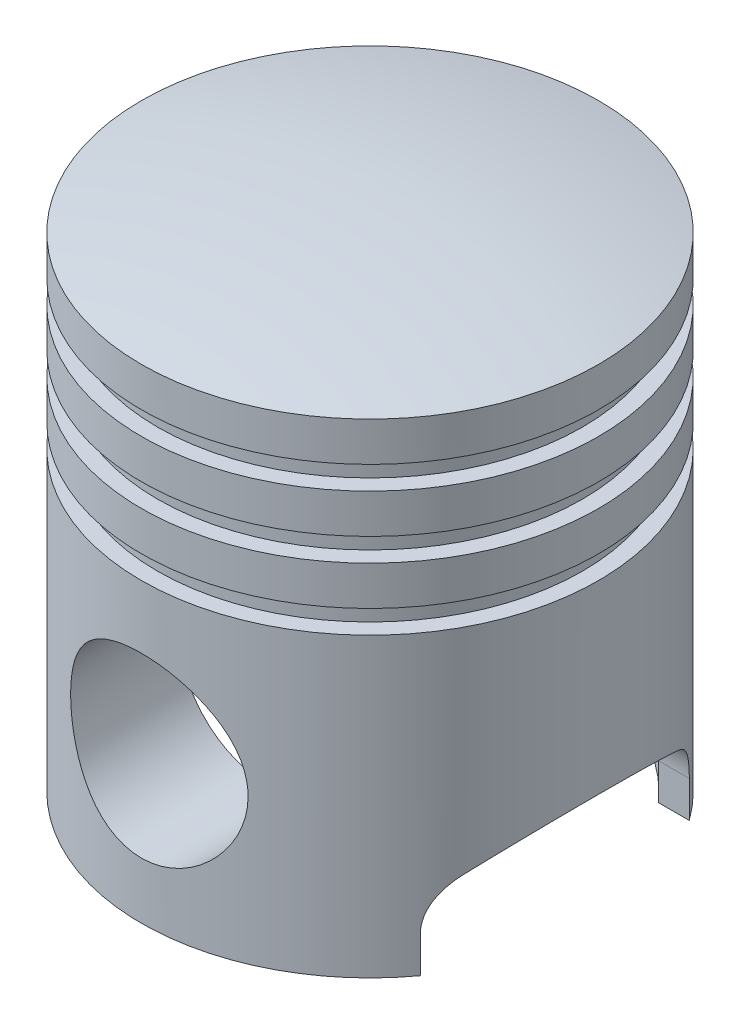
SolidWorks part; units mm, degrees
ref_plane "Front Plane" through (0, 0, 0) normal (0, 0, 1) x (1, 0, 0)
ref_plane "Top Plane" through (0, 0, 0) normal (0, 1, 0) x (1, 0, 0)
ref_plane "Right Plane" through (0, 0, 0) normal (1, 0, 0) x (0, 0, -1)
sketch "Sketch1" plane through (0, 0, 0) normal (0, 1, 0) x (1, 0, 0)
  circle A0 centre (0, 0) radius 42.5
  dimension "D1" = 85
extrude "Boss-Extrude3" add sketch "Sketch1" along normal blind 90
sketch "Sketch3" plane through (0, 90, 0) normal (0, 1, 0) x (1, 0, 0)
  circle A0 centre (0, 0) radius 39.5
  dimension "D1" = 79
extrude "Cut-Extrude2" cut sketch "Sketch3" against normal blind 4.3 from offset 7.3 flip side to cut offset against normal yes
pattern_linear "LPattern1" count 3 spacing 11.6 along (0, -1, 0) of "Cut-Extrude2"
sketch "Sketch4" plane through (0, 0, 0) normal (0, -1, 0) x (1, 0, 0)
  circle A0 centre (0, 0) radius 38
  dimension "D1" = 76
extrude "Cut-Extrude3" cut sketch "Sketch4" against normal blind 85
dome "Dome1" faces to dome 1 distance 5 reverse direction no elliptical dome no face at (0, 90, 42.5) parameters "D1"=5
sketch "Sketch5" plane through (0, 0, 0) normal (0, 0, 1) x (1, 0, 0)
  circle A0 centre (0, 27) radius 16.5
  point P2 (0, 0)
  point P4 (0, 0)
  point P5 (-0.7949, 27.2962)
  point P6 (0, 0)
  point P7 (0, 0)
  point P8 (0, 0)
  point P9 (0, 0)
  point P10 (0, 0)
  dimension "D1" = 33
  dimension "D2" = 27
extrude "Cut-Extrude4" cut sketch "Sketch5" against normal through all both and the other way through all
sketch "Sketch6" plane through (0, 0, 0) normal (1, 0, 0) x (0, 0, -1)
  line L0 (0, 0) -> (0, 25.4414) construction
  line L1 (-25, 0) -> (-25, 12)
  line L2 (-42.5, 0) -> (42.5, 0) construction
  line L3 (25, 0) -> (25, 12)
  line L4 (-25, 0) -> (25, 0)
  arc A0 (-25, 12) -> (25, 12) centre (0, -19.225) cw
  dimension "D4" = 40
  dimension "D1" = 12
  dimension "D2" = 12
  dimension "D3" = 50
extrude "Cut-Extrude6" cut sketch "Sketch6" against normal through all both and the other way through all
fillet "Fillet1" radius 10 2 edges at (-31.4937, 12, 25) (31.4937, 12, 25)
fillet "Fillet2" radius 10 2 edges at (-31.4937, 12, -25) (31.4937, 12, -25)
sketch "Sketch7" plane through (0, 0, 0) normal (0, 0, 1) x (1, 0, 0)
  circle A0 centre (0, 27) radius 16.5 construction
  circle A1 centre (0, 27) radius 16.5
  circle A2 centre (0, 27) radius 22.5
  dimension "D1" = 45
extrude "Boss-Extrude5" add sketch "Sketch7" along normal up to next from offset 19
mirror "Mirror1" about plane through (0, 0, 0) normal (0, 0, 1) of "Boss-Extrude5"
equation "\"4.3mmmm\"=90"
